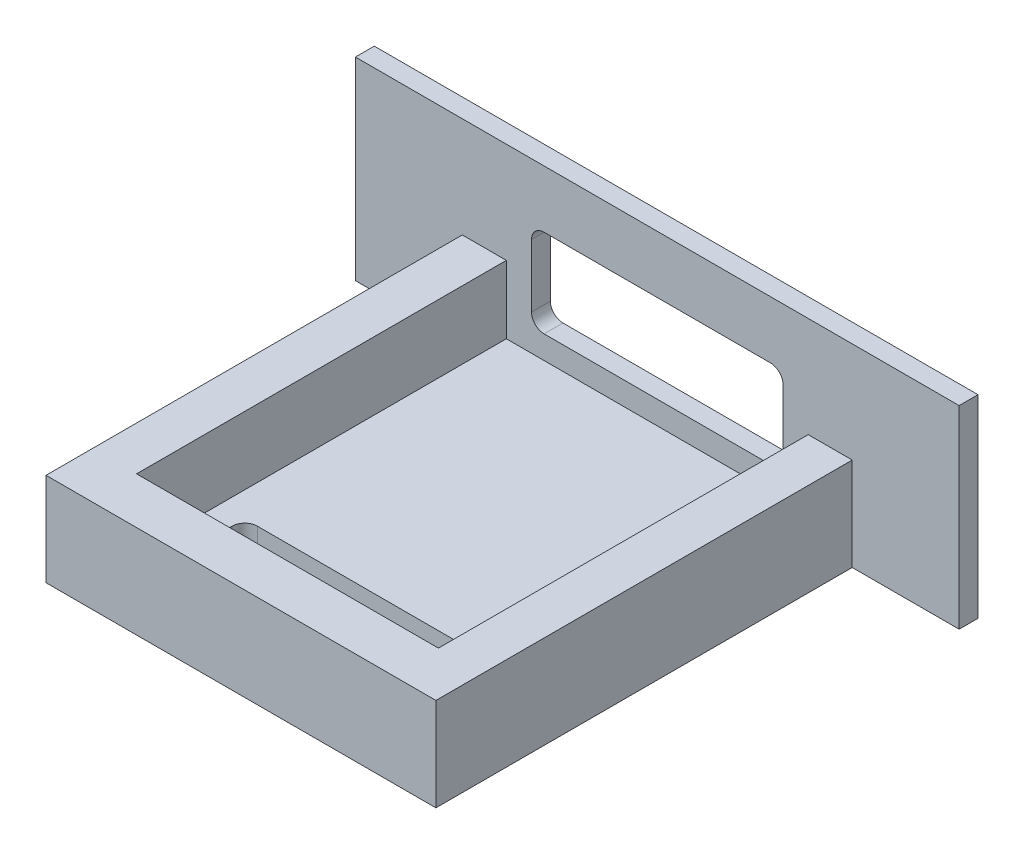
SolidWorks part; units mm, degrees
ref_plane "Front Plane" through (0, 0, 0) normal (0, 0, 1) x (1, 0, 0)
ref_plane "Top Plane" through (0, 0, 0) normal (0, 1, 0) x (1, 0, 0)
ref_plane "Right Plane" through (0, 0, 0) normal (1, 0, 0) x (0, 0, -1)
other "Graphic1"
other "Graphic (Closed) -1"
sketch "Sketch3" plane through (0, 0, 0) normal (0, 0, 1) x (1, 0, 0)
  line L1 (-4.4998, 1.1486) -> (4.5003, 1.1486)
  line L2 (-4.9998, 1.6486) -> (-4.9998, 4.1487)
  line L3 (-4.4998, 4.6487) -> (4.5003, 4.6487)
  line L4 (5.0003, 1.6486) -> (5.0003, 4.1487)
  arc A0 (4.5003, 1.1486) -> (5.0003, 1.6486) centre (4.5003, 1.6486) ccw
  arc A1 (-4.9998, 4.1487) -> (-4.4998, 4.6487) centre (-4.4998, 4.1487) cw
  arc A2 (4.5003, 4.6487) -> (5.0003, 4.1487) centre (4.5003, 4.1487) cw
  arc A3 (-4.4998, 1.1486) -> (-4.9998, 1.6486) centre (-4.4998, 1.6486) cw
  point P4 (-5.02, -1.7492)
  point P5 (4.9881, 1.7578)
  point P6 (5.0003, 1.7502)
  point P7 (-4.9998, -1.75)
  dimension "D1" = 0.5
sketch "Sketch4" plane through (0, 0, 0) normal (0, 1, 0) x (1, 0, 0)
  line L0 (-6.75, -15.3241) -> (-6.75, -0.0241)
  line L1 (-6, -14.5741) -> (6, -14.5741)
  line L2 (-6, -14.5741) -> (-6, -0.7741)
  line L3 (-6, -0.7741) -> (6, -0.7741)
  line L4 (6, -14.5741) -> (6, -0.7741)
  line L5 (-6, -14.5741) -> (6, -0.7741) construction
  line L6 (-6, -0.7741) -> (6, -14.5741) construction
  line L7 (-6.75, -0.0241) -> (6.75, -0.0241)
  line L8 (6.75, -15.3241) -> (6.75, -0.0241)
  line L9 (-6.75, -15.3241) -> (6.75, -15.3241)
  point P0 (0, -7.6741)
  point P5 (0, -8.5359)
  point P6 (0, -7.6741)
  dimension "D1" = 12
  dimension "D2" = 13.8
  dimension "D3" = 0.75
extrude "Boss-Extrude1" add sketch "Sketch4" along normal blind 2.7
sketch "Sketch5" plane through (0, 0, 0) normal (0, -1, 0) x (1, 0, 0)
  line L0 (6.75, 0.0241) -> (-6.75, 0.0241) construction
  line L1 (6.75, 15.3241) -> (6.75, 0.0241) construction
  line L2 (-6.75, 15.3241) -> (6.75, 15.3241) construction
  line L3 (-6.75, 0.0241) -> (-6.75, 15.3241) construction
  line L4 (6.75, 0.0241) -> (-6.75, 0.0241)
  line L5 (6.75, 15.3241) -> (6.75, 0.0241)
  line L6 (-6.75, 15.3241) -> (6.75, 15.3241)
  line L7 (-6.75, 0.0241) -> (-6.75, 15.3241)
extrude "Boss-Extrude2" add sketch "Sketch5" along normal blind 1
sketch "Sketch6" plane through (0, 2.7, 0) normal (0, 1, 0) x (1, 0, 0)
  line L0 (6.75, -0.0241) -> (-6.75, -0.0241) construction
  line L2 (6, -0.7741) -> (-6, -0.7741) construction
  line L3 (-12, -0.0241) -> (12, -0.0241)
  line L4 (-12, -0.0241) -> (-12, -0.7741)
  line L5 (-12, -0.7741) -> (12, -0.7741)
  line L6 (12, -0.0241) -> (12, -0.7741)
  point P4 (0, 0)
  dimension "D1" = 24
extrude "Boss-Extrude3" add sketch "Sketch6" along normal blind 4
sketch "Sketch7" plane through (0, 0, 0.0241) normal (0, 0, -1) x (-1, 0, 0)
  line L0 (-6, 0) -> (6, 0) construction
  line L1 (-6, 0) -> (6, 0) construction
  line L2 (-6, 0.919) -> (6, 0.919) construction
  line L3 (0, 0.4839) -> (5, 0.4839) construction
  line L4 (-4.5, 0.919) -> (4.5, 0.919)
  line L5 (-5, 1.419) -> (-5, 3.919)
  line L6 (-4.5, 4.419) -> (4.5, 4.419)
  line L7 (5, 1.419) -> (5, 3.919)
  arc A0 (-4.5, 0.919) -> (-5, 1.419) centre (-4.5, 1.419) cw
  arc A1 (4.5, 0.919) -> (5, 1.419) centre (4.5, 1.419) ccw
  arc A2 (4.5, 4.419) -> (5, 3.919) centre (4.5, 3.919) cw
  arc A3 (-5, 3.919) -> (-4.5, 4.419) centre (-4.5, 3.919) cw
  point P10 (4.5314, 0.5007)
  point P11 (0, 0.4839)
  point P12 (0, 0)
  point P13 (0, 0.4839)
  point P16 (-5, 0.919)
  point P19 (5, 0.919)
  point P22 (5, 4.419)
  point P25 (-5, 4.419)
  dimension "D5" = 0.5
  dimension "D1" = 0.919
  dimension "D2" = 3.5
  dimension "D3" = 10
  dimension "D4" = 5
extrude "Cut-Extrude1" cut sketch "Sketch7" against normal up to next
sketch "Sketch8" plane through (0, 2.7, 0) normal (0, -1, 0) x (1, 0, 0)
  line L4 (12, 0.7741) -> (6.75, 0.7741)
  line L5 (6.75, 0.7741) -> (6.75, 0.0241)
  line L6 (6.75, 0.0241) -> (12, 0.0241)
  line L7 (12, 0.0241) -> (12, 0.7741)
  line L8 (12, 0.7741) -> (6.75, 0.7741)
  line L9 (6.75, 0.7741) -> (6.75, 0.0241)
  line L10 (6.75, 0.0241) -> (12, 0.0241)
  line L11 (12, 0.0241) -> (12, 0.7741)
  dimension "D1" = 0
extrude "Boss-Extrude4" add sketch "Sketch8" along normal up to vertex (3.7 mm away) up to point (6.75, -1, 0.0241)
sketch "Sketch9" plane through (0, 2.7, 0) normal (0, -1, 0) x (1, 0, 0)
  line L4 (-12, 0.0241) -> (-6.75, 0.0241)
  line L5 (-6.75, 0.0241) -> (-6.75, 0.7741)
  line L6 (-6.75, 0.7741) -> (-12, 0.7741)
  line L7 (-12, 0.7741) -> (-12, 0.0241)
  line L8 (-12, 0.0241) -> (-6.75, 0.0241)
  line L9 (-6.75, 0.0241) -> (-6.75, 0.7741)
  line L10 (-6.75, 0.7741) -> (-12, 0.7741)
  line L11 (-12, 0.7741) -> (-12, 0.0241)
  dimension "D1" = 0
extrude "Boss-Extrude5" add sketch "Sketch9" along normal up to vertex (3.7 mm away) up to point (-6.75, -1, 0.0241)
sketch "Sketch10" plane through (0, 0, 15.3241) normal (0, 0, 1) x (1, 0, 0)
  line L4 (-6.75, 2.7) -> (-6.75, -1)
  line L5 (-6.75, -1) -> (6.75, -1)
  line L6 (6.75, -1) -> (6.75, 2.7)
  line L7 (6.75, 2.7) -> (-6.75, 2.7)
  line L8 (-6.75, 2.7) -> (-6.75, -1)
  line L9 (-6.75, -1) -> (6.75, -1)
  line L10 (6.75, -1) -> (6.75, 2.7)
  line L11 (6.75, 2.7) -> (-6.75, 2.7)
  dimension "D1" = 0
extrude "Boss-Extrude6" add sketch "Sketch10" along normal blind 2
chamfer "Chamfer1" distance 0.9 distance2 2.7 1 edges at (0, 2.7, 14.5741) first distance on face at (0, 2.7, 8.3616)
sketch "Sketch11" plane through (6.75, 0, 0) normal (1, 0, 0) x (0, 0, -1)
  line L4 (-17.3241, -1) -> (-0.7741, -1)
  line L5 (-0.7741, -1) -> (-0.7741, 2.7)
  line L6 (-0.7741, 2.7) -> (-17.3241, 2.7)
  line L7 (-17.3241, 2.7) -> (-17.3241, -1)
  line L8 (-17.3241, -1) -> (-0.7741, -1)
  line L9 (-0.7741, -1) -> (-0.7741, 2.7)
  line L10 (-0.7741, 2.7) -> (-17.3241, 2.7)
  line L11 (-17.3241, 2.7) -> (-17.3241, -1)
  dimension "D1" = 0
extrude "Boss-Extrude7" add sketch "Sketch11" along normal blind 1
sketch "Sketch12" plane through (-6.75, 0, 0) normal (-1, 0, 0) x (0, 0, 1)
  line L4 (0.7741, 2.7) -> (0.7741, -1)
  line L5 (0.7741, -1) -> (17.3241, -1)
  line L6 (17.3241, -1) -> (17.3241, 2.7)
  line L7 (17.3241, 2.7) -> (0.7741, 2.7)
  line L8 (0.7741, 2.7) -> (0.7741, -1)
  line L9 (0.7741, -1) -> (17.3241, -1)
  line L10 (17.3241, -1) -> (17.3241, 2.7)
  line L11 (17.3241, 2.7) -> (0.7741, 2.7)
  dimension "D1" = 0
extrude "Boss-Extrude8" add sketch "Sketch12" along normal blind 1
sketch "Sketch13" plane through (0, 0, 0) normal (0, 1, 0) x (1, 0, 0)
  line L0 (-6, -0.7741) -> (-6, -14.5741) construction
  line L1 (-4.5, -12.1741) -> (4.5, -12.1741)
  line L2 (-5, -12.6741) -> (-5, -13.0741)
  line L3 (-4.5, -13.5741) -> (4.5, -13.5741)
  line L4 (5, -12.6741) -> (5, -13.0741)
  line L5 (6, -15.4741) -> (6, -0.7741) construction
  line L6 (-6, -14.5741) -> (6, -14.5741) construction
  arc A0 (4.5, -13.5741) -> (5, -13.0741) centre (4.5, -13.0741) ccw
  arc A1 (4.5, -12.1741) -> (5, -12.6741) centre (4.5, -12.6741) cw
  arc A2 (-5, -13.0741) -> (-4.5, -13.5741) centre (-4.5, -13.0741) ccw
  arc A3 (-4.5, -12.1741) -> (-5, -12.6741) centre (-4.5, -12.6741) ccw
  point P16 (-5, -13.5741)
  point P19 (-5, -12.1741)
  dimension "D5" = 0.5
  dimension "D1" = 1
  dimension "D2" = 1
  dimension "D3" = 1
  dimension "D4" = 1.4
extrude "Cut-Extrude2" cut sketch "Sketch13" against normal up to next
